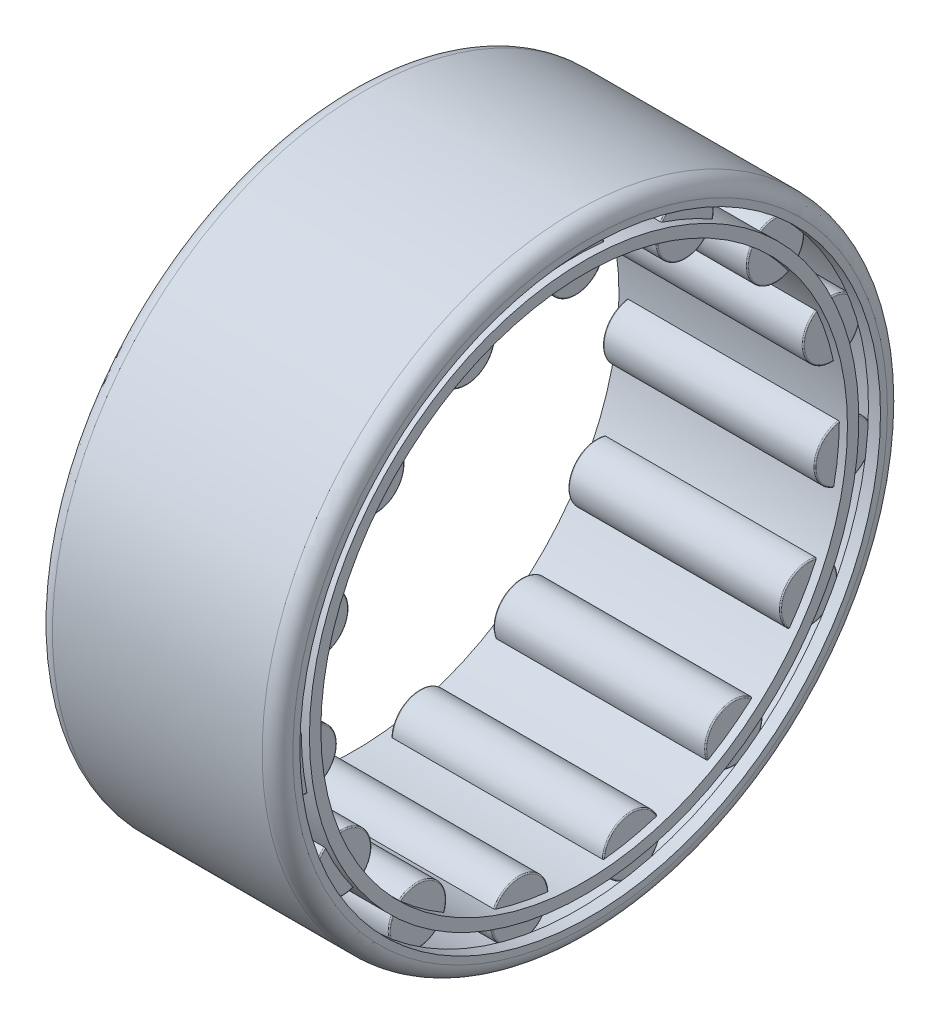
SolidWorks part; units mm, degrees
ref_plane "Plane1" through (0, 0, 0) normal (0, 0, 1) x (1, 0, 0)
ref_plane "Plane2" through (0, 0, 0) normal (0, 1, 0) x (1, 0, 0)
ref_plane "Plane3" through (0, 0, 0) normal (1, 0, 0) x (0, 0, -1)
sketch "Clipboard" plane through (0, 0, 0) normal (0, 0, 1) x (1, 0, 0)
  line L0 (-10, 0) -> (10, 0) construction
  line L1 (41.1529, 1.4371) -> (62.7517, -4.3503)
  line L2 (41.1529, 1.4371) -> (75.4583, 10.6292)
  line L3 (41.1529, 1.4371) -> (62.7517, -4.3503)
  line L4 (41.1529, 1.4371) -> (-22.3471, -0.7804)
  dimension "BallCLRad" = 35.5155
  dimension "Bore" = 63.5
sketch "InnRacSke" plane through (0, 0, 0) normal (0, 0, 1) x (1, 0, 0)
  line L0 (-14.2875, 38.3286) -> (-15.875, 38.3286)
  line L1 (-15.875, 38.3286) -> (-15.875, 39.243)
  line L2 (-13.843, 41.275) -> (13.843, 41.275)
  line L4 (15.875, 39.243) -> (15.875, 38.3286)
  line L5 (15.875, 38.3286) -> (14.2875, 38.3286)
  line L6 (14.2875, 38.3286) -> (14.2875, 39.2811)
  line L7 (14.2875, 39.2811) -> (-14.2875, 39.2811)
  line L8 (-14.2875, 39.2811) -> (-14.2875, 38.3286)
  line L9 (-31.75, 0) -> (31.75, 0) construction
  arc A0 (-15.875, 39.243) -> (-13.843, 41.275) centre (-13.843, 39.243) cw
  arc A2 (13.843, 41.275) -> (15.875, 39.243) centre (13.843, 39.243) cw
  dimension "D1" = 78.5622
revolve "Race" add sketch "InnRacSke" angle 360 about L9 reverse direction yes
sketch "RolDetSke" plane through (0, 0, 0) normal (0, 0, 1) x (1, 0, 0)
  line L0 (-14.0018, 39.131) -> (-14.0017, 35.5155)
  line L1 (-14.0017, 35.5155) -> (14.0017, 35.5155)
  line L2 (14.0017, 35.5155) -> (14.0018, 39.131)
  line L3 (13.8511, 39.2816) -> (-13.8511, 39.2816)
  line L4 (-28.575, 35.5155) -> (28.575, 35.5155) construction
  arc A0 (14.0018, 39.131) -> (13.8511, 39.2816) centre (13.8511, 39.131) ccw
  arc A1 (-13.8511, 39.2816) -> (-14.0018, 39.131) centre (-13.8511, 39.131) ccw
  dimension "Roller_length" = 28.0035
  dimension "Roller_diameter" = 7.5321
revolve "RollerDetailed" add sketch "RolDetSke" angle 360 about L4 reverse direction yes
ref_axis "Axis1" through (-50, 0, 0) along (1, 0, 0)
sketch "CagSpiSke" plane through (0, 0, 0) normal (0, 0, 1) x (1, 0, 0)
  line L0 (15.0812, 34.7623) -> (15.0812, 36.2688)
  line L1 (15.0812, 36.2688) -> (-15.0813, 36.2688)
  line L2 (-15.0813, 36.2688) -> (-15.0813, 34.7623)
  line L3 (-15.0813, 34.7623) -> (15.0812, 34.7623)
  line L4 (-31.75, 0) -> (31.75, 0) construction
  dimension "D2" = 69.5247
  dimension "halfWidth" = 15.0813
revolve "CageSpine" add sketch "CagSpiSke" angle 360 about L4
pattern_circular "RollersDetailed" count 15 every 24 about axis through (-50, 0, 0) along (1, 0, 0) of "RollerDetailed"
sketch "RolSimSke" plane through (0, 0, 0) normal (0, 0, 1) x (1, 0, 0)
  line L0 (-25.4, 0) -> (25.4, 0) construction
  line L2 (-13.8511, 39.2821) -> (13.8511, 39.2821)
  line L3 (-14.0018, 39.1315) -> (-14.0018, 31.9006)
  line L4 (-13.8511, 31.75) -> (13.8511, 31.75)
  line L5 (14.0017, 39.1315) -> (14.0017, 31.9006)
  arc A0 (-14.0018, 31.9006) -> (-13.8511, 31.75) centre (-13.8511, 31.9006) ccw
  arc A1 (-13.8511, 39.2821) -> (-14.0018, 39.1315) centre (-13.8511, 39.1315) ccw
  arc A2 (14.0017, 39.1315) -> (13.8511, 39.2821) centre (13.8511, 39.1315) ccw
  arc A3 (13.8511, 31.75) -> (14.0017, 31.9006) centre (13.8511, 31.9006) ccw
  point P10 (-14.0018, 31.75)
  point P15 (14.0017, 39.2821)
  point P18 (14.0017, 31.75)
  dimension "Bore" = 63.5
  dimension "D1" = 0.1506
  dimension "Roller_length" = 28.0035
  dimension "Roller_diameter" = 7.5321
  dimension "halfWidth" = 14.0017
revolve "RollersSimplified" [suppressed] add sketch "RolSimSke" angle 360 about L0
equation "\"BallCLRad@Clipboard\" =  ( \"D1@InnRacSke\" + \"Bore@Clipboard\" )  / 4"
equation "\"RollerCLRad@RolDetSke\" = \"BallCLRad@Clipboard\""
equation "\"halfCyl@InnRacSke\" = \"Cyl_Len@InnRacSke\" / 2"
equation "\"Roller_diameter@RolDetSke\" =  ( \"D1@InnRacSke\" - \"Bore@Clipboard\" )  / 2 + .001"
equation "\"Roller_radius@RolDetSke\" = \"Roller_diameter@RolDetSke\" / 50"
equation "\"Roller_length@RolDetSke\" = \"Cyl_Len@InnRacSke\" * .98"
equation "\"halfLength@RolDetSke\" = \"Roller_length@RolDetSke\" / 2"
equation "\"Cage_width@CagSpiSke\" =  ( \"Cyl_Len@InnRacSke\" + \"Width@InnRacSke\" )  / 2"
equation "\"halfWidth@CagSpiSke\" = \"Cage_width@CagSpiSke\" / 2"
equation "\"Cage_thickness@CagSpiSke\"  = \"Roller_diameter@RolDetSke\" / 5"
equation "\"D2@CagSpiSke\" =  \"RollerCLRad@RolDetSke\" * 2 - \"Cage_thickness@CagSpiSke\""
equation "\"Roller_length@RolSimSke\" = \"Cyl_Len@InnRacSke\" * .98"
equation "\"halfWidth@RolSimSke\" = \"Roller_length@RolSimSke\" / 2"
equation "\"D1@RolSimSke\" = \"Roller_radius@RolDetSke\""
equation "\"Roller_diameter@RolSimSke\" =  ( \"D1@InnRacSke\" - \"Bore@Clipboard\" )  / 2 + .001"
equation "\"Max_count@Clipboard\" = int( 3.14159265 / atn(( \"Roller_diameter@RolDetSke\" / 2) / sqr( \"RollerCLRad@RolDetSke\"  *  \"RollerCLRad@RolDetSke\" - ( \"Roller_diameter@RolDetSke\" / 2) *  ( \"Roller_diameter@RolDetSke\" / 2))))"
equation "\"Max_count@Clipboard\" = ((sgn( \"Max_count@Clipboard\" - \"Count@Clipboard\" )-1)*( \"Max_count@Clipboard\" - \"Count@Clipboard\" ))/-2+ \"Count@Clipboard\""
equation "\"Count@RollersDetailed\" = int( \"Show_count@Clipboard\" ) "
equation "\"Count@RollersDetailed\" = ((sgn( \"Count@RollersDetailed\" - \"Max_count@Clipboard\" )-1)*( \"Count@RollersDetailed\" - \"Max_count@Clipboard\" ))/-2+ \"Max_count@Clipboard\""
equation "\"Count@RollersDetailed\" = ((sgn( \"Count@RollersDetailed\" - \"Min_count@Clipboard\" )+1)*( \"Count@RollersDetailed\" - \"Min_count@Clipboard\"))/2 +\"Min_count@Clipboard\""
equation "\"Angle@RollersDetailed\" = 360.0 / \"Max_count@Clipboard\""
equation "\"Angle@CageSpine\" =  \"Angle@RollersDetailed\" * ( \"Count@RollersDetailed\" -1 + int( \"Count@RollersDetailed\" / \"Max_count@Clipboard\" ) )  + 0.001 -  int( \"Count@RollersDetailed\" / \"Max_count@Clipboard\" ) * 0.001"
equation "\"Angle@CageSpine\" =  \"Angle@CageSpine\" * int( \"Min_count@Clipboard\" / 2) + int(1 / \"Min_count@Clipboard\")  * 0.001"
equation "\"Bore@RolSimSke\" = \"Bore@Clipboard\""
